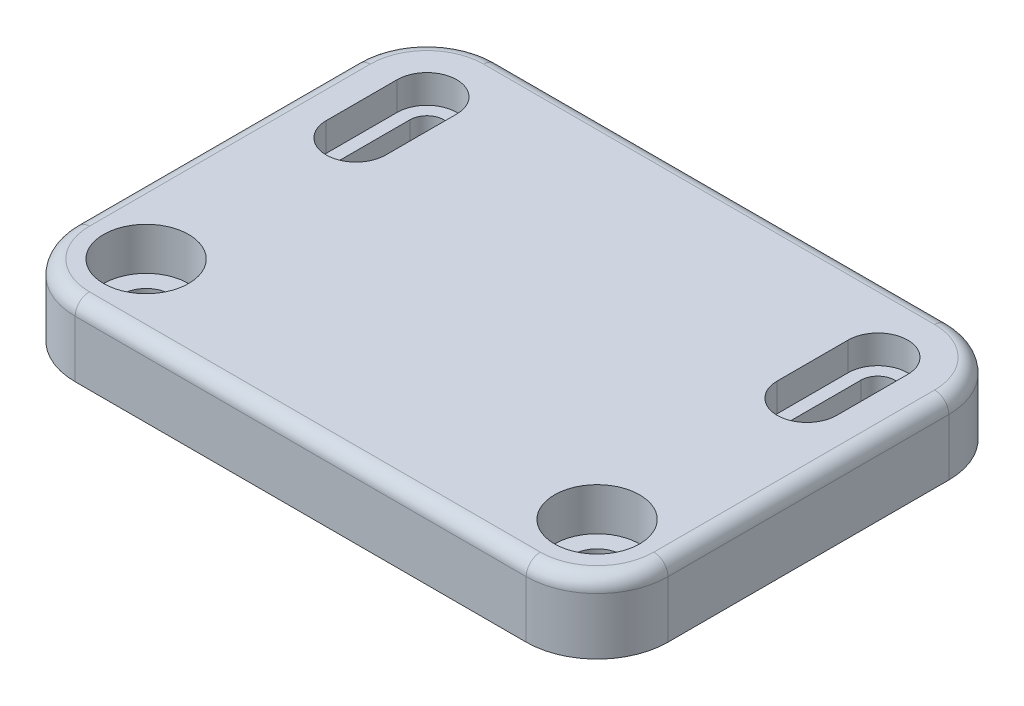
SolidWorks part; units mm, degrees
ref_plane "Front Plane" through (0, 0, 0) normal (0, 0, 1) x (1, 0, 0)
ref_plane "Top Plane" through (0, 0, 0) normal (0, 1, 0) x (1, 0, 0)
ref_plane "Right Plane" through (0, 0, 0) normal (1, 0, 0) x (0, 0, -1)
sketch "Sketch1" plane through (0, 0, 0) normal (0, 1, 0) x (1, 0, 0)
  line L0 (5, 19.8) -> (5, 24.8) construction
  line L1 (0, 0) -> (41.8, 0)
  line L2 (0, 0) -> (0, 29.8)
  line L3 (0, 29.8) -> (41.8, 29.8)
  line L4 (41.8, 0) -> (41.8, 29.8)
  line L5 (5, 19.8) -> (36.8, 19.8) construction
  line L6 (5, 19.8) -> (5, 5) construction
  line L7 (5, 5) -> (36.8, 5) construction
  line L8 (36.8, 19.8) -> (36.8, 5) construction
  line L9 (3.8, 19.8) -> (3.8, 24.8)
  line L10 (6.2, 19.8) -> (6.2, 24.8)
  line L11 (36.8, 19.8) -> (36.8, 24.8) construction
  line L12 (35.6, 19.8) -> (35.6, 24.8)
  line L13 (38, 19.8) -> (38, 24.8)
  line L14 (0, 0) -> (5, 5) construction
  line L15 (36.8, 5) -> (41.8, 0) construction
  circle A0 centre (5, 5) radius 1.7
  circle A1 centre (36.8, 5) radius 1.7
  arc A2 (3.8, 19.8) -> (6.2, 19.8) centre (5, 19.8) ccw
  arc A3 (6.2, 24.8) -> (3.8, 24.8) centre (5, 24.8) ccw
  arc A4 (35.6, 19.8) -> (38, 19.8) centre (36.8, 19.8) ccw
  arc A5 (38, 24.8) -> (35.6, 24.8) centre (36.8, 24.8) ccw
  point P11 (5, 22.3)
  point P17 (36.8, 22.3)
  dimension "D1" = 1.2
  dimension "D2" = 3.4
  dimension "D3" = 31.8
  dimension "D4" = 14.8
  dimension "D5" = 5
  dimension "D6" = 5
  dimension "D7" = 5
  dimension "D8" = 5
extrude "Boss-Extrude1" add sketch "Sketch1" along normal blind 5
fillet "Fillet1" radius 5 4 edges at (0, 2.5, -29.8) (41.8, 2.5, -29.8) (41.8, 2.5, 0) (0, 2.5, 0)
fillet "Fillet2" radius 1 8 edges at (1.4645, 5, -1.4645) (0, 5, -14.9) (1.4645, 5, -28.3355) (20.9, 5, -29.8) (40.3355, 5, -28.3355) (41.8, 5, -14.9) (40.3355, 5, -1.4645) (20.9, 5, 0)
sketch "Sketch2" plane through (0, 5, 0) normal (0, 1, 0) x (1, 0, 0)
  line L0 (5, 24.8) -> (5, 19.8) construction
  line L1 (7.1, 24.8) -> (7.1, 19.8)
  line L2 (2.9, 24.8) -> (2.9, 19.8)
  line L3 (36.8, 24.8) -> (36.8, 19.8) construction
  line L4 (38.9, 24.8) -> (38.9, 19.8)
  line L5 (34.7, 24.8) -> (34.7, 19.8)
  circle A0 centre (5, 5) radius 3
  circle A1 centre (36.8, 5) radius 3
  arc A2 (7.1, 24.8) -> (2.9, 24.8) centre (5, 24.8) ccw
  arc A3 (2.9, 19.8) -> (7.1, 19.8) centre (5, 19.8) ccw
  arc A4 (38.9, 24.8) -> (34.7, 24.8) centre (36.8, 24.8) ccw
  arc A5 (34.7, 19.8) -> (38.9, 19.8) centre (36.8, 19.8) ccw
  point P10 (5, 22.3)
  point P15 (36.8, 22.3)
  arc M18 (6.2, 19.8) -> (3.8, 19.8) centre (5, 19.8) cw
  line M19 (3.8, 19.8) -> (3.8, 24.8)
  arc M20 (3.8, 24.8) -> (6.2, 24.8) centre (5, 24.8) cw
  line M21 (6.2, 24.8) -> (6.2, 19.8)
  circle M22 centre (5, 5) radius 1.7
  circle M23 centre (36.8, 5) radius 1.7
  arc M24 (38, 19.8) -> (35.6, 19.8) centre (36.8, 19.8) cw
  line M25 (35.6, 19.8) -> (35.6, 24.8)
  arc M26 (35.6, 24.8) -> (38, 24.8) centre (36.8, 24.8) cw
  line M27 (38, 24.8) -> (38, 19.8)
  dimension "D1" = 6
  dimension "D2" = 2.1
extrude "Cut-Extrude1" cut sketch "Sketch2" against normal blind 3 contours A0 M22 | A1 M23 region at (2.0849, 5, -5) region at (33.8849, 5, -5)
extrude "Cut-Extrude2" cut sketch "Sketch2<3>" against normal blind 2 contours L2 A3 L1 A2 M21 M18 M19 M20 | L5 A5 L4 A4 M27 M24 M25 M26 region at (6.9989, 5, -22.3) region at (38.7989, 5, -22.3)
sketch "Sketch2<3>" plane through (0, 5, 0) normal (0, 1, 0) x (1, 0, 0) same geometry as "Sketch2"
